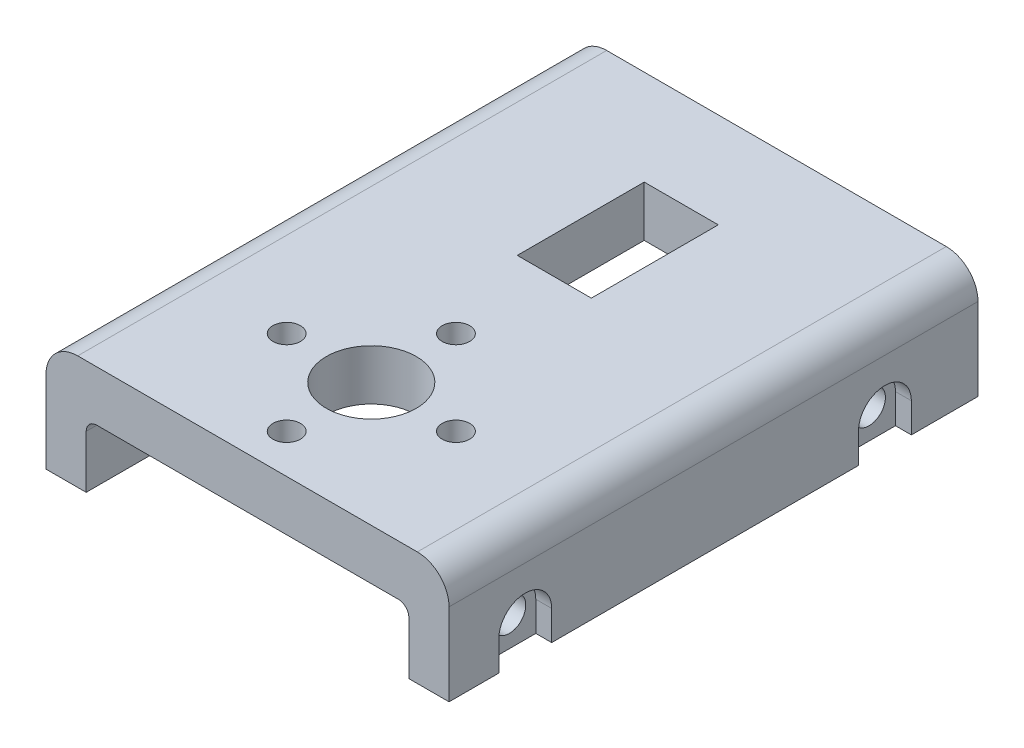
SolidWorks part; units mm, degrees
material "Onyx w/ CF"
ref_plane "Front Plane" through (0, 0, 0) normal (0, 0, 1) x (1, 0, 0)
ref_plane "Top Plane" through (0, 0, 0) normal (0, 1, 0) x (1, 0, 0)
ref_plane "Right Plane" through (0, 0, 0) normal (1, 0, 0) x (0, 0, -1)
sketch "Sketch1" plane through (0, 0, 0) normal (1, 0, 0) x (0, 0, -1)
  line L3 (-25, -10.775) -> (-25, 0)
  line L4 (-25, 0) -> (25, 0)
  line L5 (25, 0) -> (25, -10.775)
  line L6 (25, -10.775) -> (-25, -10.775)
  point P4 (0, 0)
  dimension "D1" = 10.775
  dimension "D2" = 50
extrude "Boss-Extrude1" add sketch "Sketch1" along normal mid plane 38.1
sketch "Sketch2" plane through (0, 0, 25) normal (0, 0, 1) x (1, 0, 0)
  line L0 (19.05, -10.775) -> (-19.05, -10.775) construction
  line L1 (-15.25, -10.775) -> (15.25, -10.775)
  line L2 (-15.25, -10.775) -> (-15.25, -4.775)
  line L3 (-15.25, -4.775) -> (15.25, -4.775)
  line L4 (15.25, -10.775) -> (15.25, -4.775)
  point P6 (0, -4.775)
  dimension "D1" = 30.5
  dimension "D2" = 6
extrude "Cut-Extrude1" cut sketch "Sketch2" against normal through all
sketch "Sketch3" plane through (0, -4.775, 0) normal (0, -1, 0) x (1, 0, 0)
  line L0 (15.25, 25) -> (-15.25, 25) construction
  circle A0 centre (0, 13.3) radius 4.25
  dimension "D2" = 8.5
  dimension "D1" = 11.7
extrude "Cut-Extrude2" cut sketch "Sketch3" against normal through all
hole_wizard "M2 Clearance Hole1" positions "Sketch4" profile "Sketch5" hole size "M2" standard "ANSI Metric" end condition through all
sketch "Sketch4" plane through (0, -4.775, 0) normal (0, -1, 0) x (-1, 0, 0)
  circle A0 centre (0, -13.3) radius 8
  circle A1 centre (0, -13.3) radius 4.25 construction
  point P0 (8, -13.3)
  point P2 (0, -21.3)
  point P4 (-8, -13.3)
  point P6 (0, -5.3)
  dimension "D1" = 16
sketch "Sketch5" plane through (-8, -4.775, 13.3) normal (1, 0, 0) x (0, 0, -1)
  line L0 (0, 0) -> (0, 4.775)
  line L1 (0, 4.775) -> (1.3, 4.775)
  line L2 (1.3, 4.775) -> (1.3, 0)
  line L5 (1.3, 0) -> (0, 0)
  line L11 (0, -6.35) -> (0, 107.95) construction
  dimension "Thru Hole Dia." = 2.6
  dimension "Thru Hole Depth" = 4.775
hole_wizard "M2.5 Clearance Hole1" positions "Sketch6" profile "Sketch7" hole size "M2.5" standard "ANSI Metric" end condition through all
sketch "Sketch6" plane through (-19.05, 0, 0) normal (-1, 0, 0) x (0, 0, 1)
  line L0 (-16.2, -7.975) -> (17.8, -7.975) construction
  line L2 (-25, -10.775) -> (25, -10.775) construction
  line L3 (-25, -4.775) -> (-25, -10.775) construction
  point P0 (-16.2, -7.975)
  point P2 (17.8, -7.975)
  dimension "D1" = 2.8
  dimension "D2" = 8.8
  dimension "D3" = 34
sketch "Sketch7" plane through (-19.05, -7.975, -16.2) normal (0, 1, 0) x (0, 0, 1)
  line L0 (0, 0) -> (0, 38.1)
  line L1 (0, 38.1) -> (1.55, 38.1)
  line L2 (1.55, 38.1) -> (1.55, 0)
  line L5 (1.55, 0) -> (0, 0)
  line L11 (0, -6.35) -> (0, 107.95) construction
  dimension "Thru Hole Dia." = 3.1
  dimension "Thru Hole Depth" = 38.1
sketch "Sketch8" plane through (19.05, 0, 0) normal (1, 0, 0) x (0, 0, -1)
  line L0 (-20.3, -7.975) -> (-20.3, -10.775)
  line L1 (-25, -10.775) -> (25, -10.775) construction
  line L2 (-20.3, -10.775) -> (-15.3, -10.775)
  line L3 (-15.3, -10.775) -> (-15.3, -7.975)
  line L4 (0, 0) -> (0, -8.775) construction
  line L5 (25, 0) -> (-25, 0) construction
  line L6 (13.7, -7.975) -> (13.7, -10.775)
  line L7 (13.7, -10.775) -> (18.7, -10.775)
  line L8 (18.7, -10.775) -> (18.7, -7.975)
  arc A0 (-15.3, -7.975) -> (-20.3, -7.975) centre (-17.8, -7.975) ccw
  circle A1 centre (-17.8, -7.975) radius 1.55 construction
  arc A2 (18.7, -7.975) -> (13.7, -7.975) centre (16.2, -7.975) ccw
  circle A3 centre (16.2, -7.975) radius 1.55 construction
  dimension "D2" = 5
extrude "Cut-Extrude3" cut sketch "Sketch8" against normal blind 1.5
extrude "Cut-Extrude4" cut sketch "Sketch8<2>" along normal blind 1.5 from surface starting at face at (-19.05, -7.975, -14.65)
sketch "Sketch8<2>" plane through (19.05, 0, 0) normal (1, 0, 0) x (0, 0, -1) same geometry as "Sketch8"
fillet "Fillet1" radius 1 2 edges at (-15.25, -4.775, 0) (15.25, -4.775, 0)
fillet "Fillet2" radius 3 2 edges at (-19.05, 0, 0) (19.05, 0, 0)
sketch "Sketch9" plane through (0, 0, 0) normal (0, 1, 0) x (1, 0, 0)
  line L0 (16.05, 25) -> (-16.05, 25) construction
  line L1 (-3.5, 16) -> (3.5, 16)
  line L2 (-3.5, 16) -> (-3.5, 4)
  line L3 (-3.5, 4) -> (3.5, 4)
  line L4 (3.5, 16) -> (3.5, 4)
  line L5 (-3.5, 16) -> (3.5, 4) construction
  line L6 (-3.5, 4) -> (3.5, 16) construction
  point P0 (0, 10)
  point P5 (0, 10.7851)
  point P7 (0, 13.5609)
  dimension "D1" = 7
  dimension "D2" = 12
  dimension "D3" = 15
extrude "Cut-Extrude5" cut sketch "Sketch9" against normal through all
